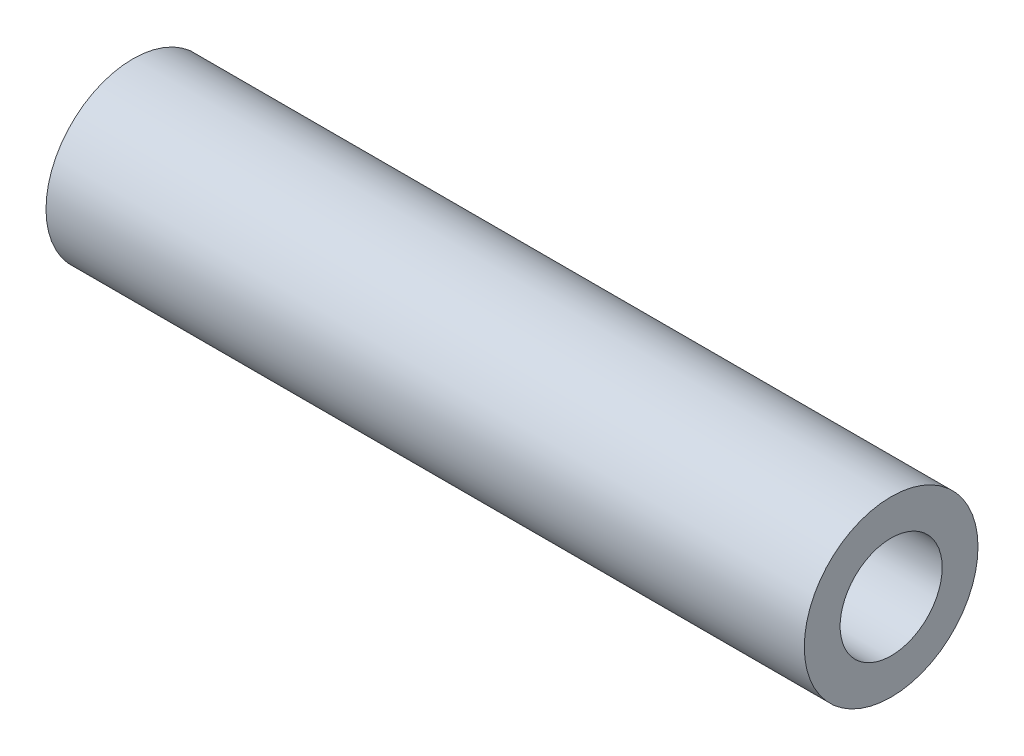
SolidWorks part; units mm, degrees
ref_plane "Front Plane" through (0, 0, 0) normal (0, 0, 1) x (1, 0, 0)
ref_plane "Top Plane" through (0, 0, 0) normal (0, 1, 0) x (1, 0, 0)
ref_plane "Right Plane" through (0, 0, 0) normal (1, 0, 0) x (0, 0, -1)
sketch "Sketch1" plane through (0, 0, 0) normal (1, 0, 0) x (0, 0, -1)
  circle A0 centre (0, 0) radius 4
  circle A1 centre (0, 0) radius 2.35
  dimension "D1" = 4.7
  dimension "D2" = 8
extrude "Boss-Extrude1" add sketch "Sketch1" along normal blind 34.925
